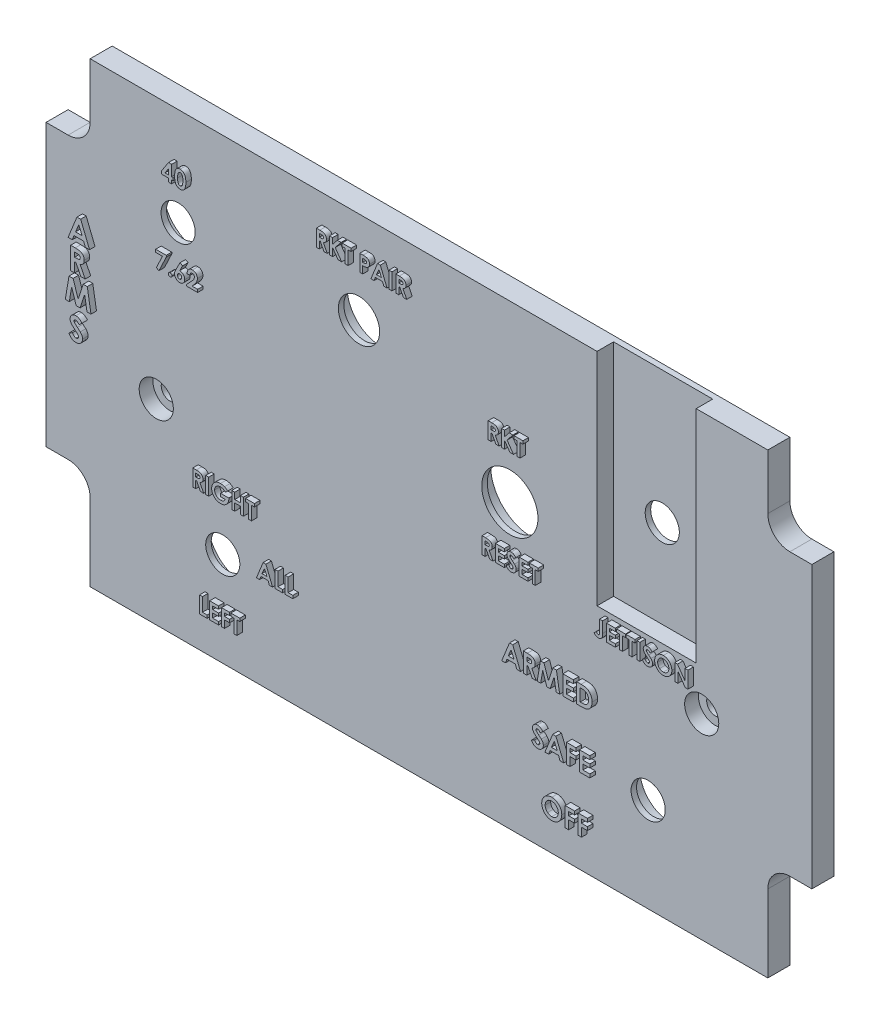
SolidWorks part; units mm, degrees
ref_plane "Front Plane" through (0, 0, 0) normal (0, 0, 1) x (1, 0, 0)
ref_plane "Top Plane" through (0, 0, 0) normal (0, 1, 0) x (1, 0, 0)
ref_plane "Right Plane" through (0, 0, 0) normal (1, 0, 0) x (0, 0, -1)
sketch "Sketch1" plane through (0, 0, 0) normal (0, 0, 1) x (1, 0, 0)
  line L1 (8, 6.6454) -> (131, 6.6454)
  line L2 (0, 24.6454) -> (0, 75.6454)
  line L3 (8, 89.6454) -> (131, 89.6454)
  line L4 (139, 24.6454) -> (139, 75.6454)
  line L13 (8, 89.6454) -> (8, 79.6454)
  line L14 (4, 75.6454) -> (0, 75.6454)
  line L15 (8, 6.6454) -> (8, 20.6454)
  line L16 (4, 24.6454) -> (0, 24.6454)
  line L17 (131, 89.6454) -> (131, 79.6454)
  line L18 (135, 75.6454) -> (139, 75.6454)
  line L19 (131, 6.6454) -> (131, 20.6454)
  line L20 (135, 24.6454) -> (139, 24.6454)
  line L23 (0, 0) -> (0, 87.0008) construction
  arc A8 (8, 20.6454) -> (4, 24.6454) centre (4, 20.6454) ccw
  arc A9 (8, 79.6454) -> (4, 75.6454) centre (4, 79.6454) cw
  arc A11 (131, 20.6454) -> (135, 24.6454) centre (135, 20.6454) cw
  arc A12 (131, 79.6454) -> (135, 75.6454) centre (135, 79.6454) ccw
  circle A14 centre (119, 42.1736) radius 1.6 construction
  circle A15 centre (109.2813, 23.7457) radius 3.1 construction
  circle A16 centre (108.8427, 65.6454) radius 3.1 construction
  circle A17 centre (84.179, 58.026) radius 5.1 construction
  circle A18 centre (56.7976, 72.9728) radius 3.75 construction
  circle A19 centre (32.0701, 23.7457) radius 3.1 construction
  circle A35 centre (20, 42.1736) radius 1.6 construction
  circle A37 centre (23.9669, 71.8931) radius 3.1 construction
  circle A38 centre (119, 42.1736) radius 1.6
  circle A40 centre (109.2813, 23.7457) radius 3.1
  circle A41 centre (108.8427, 65.6454) radius 3.1
  circle A42 centre (84.179, 58.026) radius 5.1
  circle A43 centre (56.7976, 72.9728) radius 3.75
  circle A44 centre (32.0701, 23.7457) radius 3.1
  circle A45 centre (20, 42.1736) radius 1.6
  circle A46 centre (23.9669, 71.8931) radius 3.1
  point P21 (131, 24.6454)
  point P25 (8, 75.6454)
  point P40 (131, 75.6454)
  dimension "D3" = 18
  dimension "D4" = 14
  dimension "D5" = 8
  dimension "D7" = 83
  dimension "D11" = 8
  dimension "D15" = 123
  dimension "D16" = 139
  dimension "D22" = 8
  dimension "D9" = 8
extrude "Boss-Extrude1" add sketch "Sketch1" along normal blind 4
sketch "Sketch5" plane through (0, 0, 0) normal (0, 0, -1) x (-1, 0, 0)
  circle A0 centre (-109.2813, 23.7457) radius 3.1 construction
  circle A1 centre (-108.8427, 65.6454) radius 3.1 construction
  circle A2 centre (-84.179, 58.026) radius 5.1 construction
  circle A3 centre (-56.7976, 72.9728) radius 3.75 construction
  circle A4 centre (-23.9669, 71.8931) radius 3.1 construction
  circle A5 centre (-32.0701, 23.7457) radius 3.1 construction
  circle A6 centre (-109.2813, 23.7457) radius 3.1 construction
  circle A7 centre (-108.8427, 65.6454) radius 3.1 construction
  circle A8 centre (-84.179, 58.026) radius 5.1 construction
  circle A9 centre (-56.7976, 72.9728) radius 3.75 construction
  circle A10 centre (-23.9669, 71.8931) radius 3.1 construction
  circle A11 centre (-32.0701, 23.7457) radius 3.1 construction
  circle A12 centre (-109.2813, 23.7457) radius 5.5
  circle A14 centre (-56.7976, 72.9728) radius 6.15
  circle A17 centre (-84.179, 58.026) radius 7.5
  circle A18 centre (-23.9669, 71.8931) radius 6.75
  circle A19 centre (-32.0701, 23.7457) radius 6.75
  circle A20 centre (-108.8427, 65.6454) radius 6.75
  circle M23 centre (-109.2813, 23.7457) radius 3.1
  circle M25 centre (-84.179, 58.026) radius 5.1
  circle M26 centre (-56.7976, 72.9728) radius 3.75
  circle M27 centre (-32.0701, 23.7457) radius 3.1
  circle M29 centre (-23.9669, 71.8931) radius 3.1
  dimension "D2" = 13.5
  dimension "D3" = 15
  dimension "D4" = 13.5
  dimension "D5" = 13.5
  dimension "D6" = 11
  dimension "D7" = 12.3
  dimension "D1" = 2.4
extrude "Back Holes" cut sketch "Sketch5" against normal blind 3 contours A12 M23 | A17 M25 | A14 M26 | A19 M27 | A18 M29 | A17 region at (114.6257, 23.7457, 0) region at (62.7736, 72.9728, 0) region at (91.4668, 58.026, 0) region at (30.526, 71.8931, 0) region at (38.6292, 23.7457, 0)
sketch "Sketch6" plane through (0, 0, 4) normal (0, 0, 1) x (1, 0, 0)
  circle A0 centre (20, 42.1736) radius 1.6 construction
  circle A1 centre (119, 42.1736) radius 1.6 construction
  circle A2 centre (20, 42.1736) radius 1.6 construction
  circle A3 centre (119, 42.1736) radius 1.6 construction
  circle A4 centre (20, 42.1736) radius 3.1
  circle A5 centre (119, 42.1736) radius 3.1
  dimension "D1" = 1.5
extrude "Cama tornillos" cut sketch "Sketch6" against normal blind 2.5
sketch "Sketch4" plane through (0, 0, 4) normal (0, 0, 1) x (1, 0, 0)
  line L0 (8, 54.5551) -> (8, 14.5758) construction
  line L1 (8, 89.6454) -> (8, 79.6454) construction
  line L2 (-3.2263, 44.852) -> (14.9404, 44.852) construction
  line L4 (-3.2263, 60.566) -> (14.9404, 60.566) construction
  line L5 (-3.2263, 55.566) -> (14.9404, 55.566) construction
  line L6 (-3.2263, 50.566) -> (14.9404, 50.566) construction
  line L7 (5, 54.5551) -> (5, 14.5758) construction
  text T0 "<b>A</b>" font "Century Gothic" height 4
  text T1 "<b>7.62</b>" font "Century Gothic" height 3
  text T2 "<b>RIGHT</b>" font "Century Gothic" height 3
  text T3 "<b>ALL</b>" font "Century Gothic" height 3
  text T4 "<b>RKT</b>" font "Century Gothic" height 3
  text T5 "<b>S</b>" font "Century Gothic" height 4
  text T6 "<b>RESET</b>" font "Century Gothic" height 3
  text T7 "<b>RKT PAIR</b>" font "Century Gothic" height 3
  text T8 "<b>40</b>" font "Century Gothic" height 3
  text T9 "<b>R</b>" font "Century Gothic" height 4
  text T10 "<b>M</b>" font "Century Gothic" height 4
  text T11 "<b>ARMED</b>" font "Century Gothic" height 3.5
  text T12 "<b>SAFE</b>" font "Century Gothic" height 3.5
  text T13 "<b>OFF</b>" font "Century Gothic" height 3.5
  text T14 "<b>LEFT</b>" font "Century Gothic" height 3
  text T15 "<b>JETTISON</b>" font "Century Gothic" height 3
  dimension "D1" = 3
  dimension "D2" = 5
  dimension "D3" = 5
extrude "Textos" add sketch "Sketch4" along normal blind 1
sketch "Sketch8" plane through (0, 0, 4) normal (0, 0, 1) x (1, 0, 0)
  line L0 (131, 79.6454) -> (131, 89.6454) construction
  line L1 (131, 89.6454) -> (8, 89.6454) construction
  line L2 (118, 89.6454) -> (99.9996, 89.6454)
  line L3 (118, 89.6454) -> (118, 49.6454)
  line L4 (118, 49.6454) -> (99.9996, 49.6454)
  line L5 (99.9996, 89.6454) -> (99.9996, 49.6454)
  dimension "D1" = 40
  dimension "D2" = 18.0004
  dimension "D3" = 13
extrude "Cut-Extrude3" cut sketch "Sketch8" against normal blind 3
